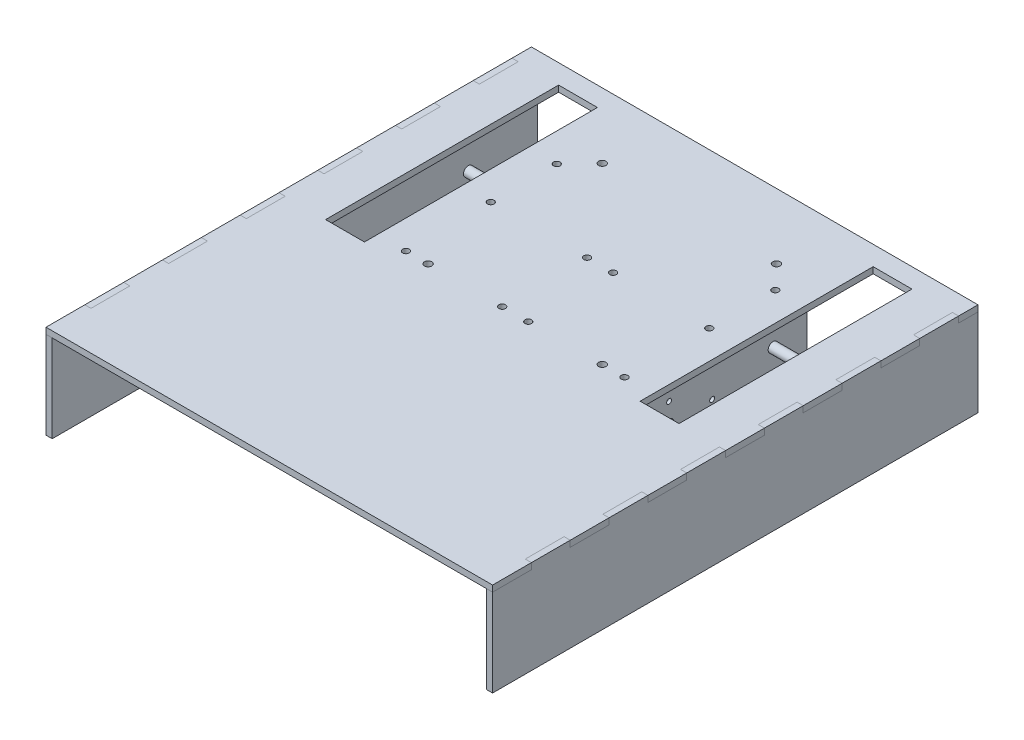
SolidWorks part; units mm, degrees
ref_plane "Front Plane" through (0, 0, 0) normal (0, 0, 1) x (1, 0, 0)
ref_plane "Top Plane" through (0, 0, 0) normal (0, 1, 0) x (1, 0, 0)
ref_plane "Right Plane" through (0, 0, 0) normal (1, 0, 0) x (0, 0, -1)
sketch "Sketch2" plane through (0, 0, 0) normal (0, 1, 0) x (1, 0, 0)
  line L7 (-172.2662, -88.2141) -> (57.7338, -88.2141)
  line L8 (13.7338, 151.7859) -> (33.7338, 151.7859)
  line L9 (57.7338, -88.2141) -> (57.7338, -68.2141)
  line L10 (57.7338, -68.2141) -> (54.5588, -68.2141)
  line L11 (54.5588, -68.2141) -> (54.5588, -48.2141)
  line L12 (54.5588, -48.2141) -> (57.7338, -48.2141)
  line L13 (-172.2662, -88.2141) -> (-172.2662, -68.2141)
  line L14 (-172.2662, -68.2141) -> (-169.0912, -68.2141)
  line L15 (-169.0912, -68.2141) -> (-169.0912, -48.2141)
  line L16 (-169.0912, -48.2141) -> (-172.2662, -48.2141)
  line L17 (-172.2662, -48.2141) -> (-172.2662, -28.2141)
  line L18 (-172.2662, -28.2141) -> (-169.0912, -28.2141)
  line L19 (-169.0912, -28.2141) -> (-169.0912, -8.2141)
  line L20 (-169.0912, -8.2141) -> (-172.2662, -8.2141)
  line L21 (57.7338, -28.2141) -> (54.5588, -28.2141)
  line L22 (54.5588, -28.2141) -> (54.5588, -8.2141)
  line L23 (54.5588, -8.2141) -> (57.7338, -8.2141)
  line L24 (57.7338, -48.2141) -> (57.7338, -28.2141)
  line L25 (-172.2662, -8.2141) -> (-172.2662, 11.7859)
  line L26 (-172.2662, 11.7859) -> (-169.0912, 11.7859)
  line L27 (-169.0912, 11.7859) -> (-169.0912, 31.7859)
  line L28 (-169.0912, 31.7859) -> (-172.2662, 31.7859)
  line L29 (57.7338, 11.7859) -> (54.5588, 11.7859)
  line L30 (54.5588, 11.7859) -> (54.5588, 31.7859)
  line L31 (54.5588, 31.7859) -> (57.7338, 31.7859)
  line L32 (57.7338, -8.2141) -> (57.7338, 11.7859)
  line L33 (-172.2662, 31.7859) -> (-172.2662, 51.7859)
  line L34 (-172.2662, 51.7859) -> (-169.0912, 51.7859)
  line L35 (-169.0912, 51.7859) -> (-169.0912, 71.7859)
  line L36 (-169.0912, 71.7859) -> (-172.2662, 71.7859)
  line L37 (57.7338, 51.7859) -> (54.5588, 51.7859)
  line L38 (54.5588, 51.7859) -> (54.5588, 71.7859)
  line L39 (54.5588, 71.7859) -> (57.7338, 71.7859)
  line L40 (57.7338, 31.7859) -> (57.7338, 51.7859)
  line L45 (13.7338, 151.7859) -> (13.7338, 31.7859)
  line L46 (13.7338, 31.7859) -> (33.7338, 31.7859)
  line L47 (33.7338, 151.7859) -> (33.7338, 31.7859)
  line L48 (-148.2662, 151.7859) -> (-128.2662, 151.7859)
  line L49 (-148.2662, 151.7859) -> (-148.2662, 31.7859)
  line L50 (-148.2662, 31.7859) -> (-128.2662, 31.7859)
  line L51 (-128.2662, 151.7859) -> (-128.2662, 31.7859)
  line L52 (-172.2662, 71.7859) -> (-172.2662, 91.7859)
  line L53 (-172.2662, 91.7859) -> (-169.0912, 91.7859)
  line L54 (-169.0912, 91.7859) -> (-169.0912, 111.7859)
  line L55 (-169.0912, 111.7859) -> (-172.2662, 111.7859)
  line L56 (57.7338, 91.7859) -> (54.5588, 91.7859)
  line L57 (54.5588, 91.7859) -> (54.5588, 111.7859)
  line L58 (54.5588, 111.7859) -> (57.7338, 111.7859)
  line L59 (57.7338, 71.7859) -> (57.7338, 91.7859)
  line L63 (-172.2662, 111.7859) -> (-172.2662, 131.7859)
  line L64 (-172.2662, 131.7859) -> (-169.0912, 131.7859)
  line L65 (-169.0912, 131.7859) -> (-169.0912, 151.7859)
  line L66 (-169.0912, 151.7859) -> (-172.2662, 151.7859)
  line L67 (57.7338, 131.7859) -> (54.5588, 131.7859)
  line L68 (54.5588, 131.7859) -> (54.5588, 151.7859)
  line L69 (54.5588, 151.7859) -> (57.7338, 151.7859)
  line L70 (57.7338, 111.7859) -> (57.7338, 131.7859)
  line L71 (57.7338, 151.7859) -> (57.7338, 161.7859)
  line L72 (57.7338, 161.7859) -> (-172.2662, 161.7859)
  line L73 (-172.2662, 161.7859) -> (-172.2662, 151.7859)
  dimension "D1" = 3.175
  dimension "D2" = 20
  dimension "D3" = 20
  dimension "D4" = 3.175
  dimension "D6" = 230
  dimension "D8" = 20
  dimension "D9" = 20
  dimension "D10" = 24
  dimension "D11" = 24
  dimension "D13" = 120
  dimension "D7" = 10
  dimension "D12" = 10
  dimension "D5" = 6
extrude "Boss-Extrude1" add sketch "Sketch2" along normal blind 3.175
ref_plane "Plane3" through (-57.2662, 0, 0) normal (-1, 0, 0) x (0, 0, 1)
sketch "Sketch3" plane through (-169.0912, 0, 0) normal (-1, 0, 0) x (0, 0, 1)
  line L0 (68.2141, 3.175) -> (68.2141, 0)
  line L1 (68.2141, 0) -> (88.2141, 0)
  line L2 (88.2141, 0) -> (88.2141, -45)
  line L3 (68.2141, 3.175) -> (48.2141, 3.175)
  line L4 (48.2141, 3.175) -> (48.2141, 0)
  line L5 (48.2141, 0) -> (28.2141, 0)
  line L6 (28.2141, 0) -> (28.2141, 3.175)
  line L7 (28.2141, 3.175) -> (8.2141, 3.175)
  line L8 (8.2141, 3.175) -> (8.2141, 0)
  line L9 (8.2141, 0) -> (-11.7859, 0)
  line L10 (-11.7859, 0) -> (-11.7859, 3.175)
  line L11 (-91.7859, 0) -> (-91.7859, 3.175)
  line L12 (-11.7859, 3.175) -> (-31.7859, 3.175)
  line L13 (-31.7859, 3.175) -> (-31.7859, 0)
  line L14 (-31.7859, 0) -> (-51.7859, 0)
  line L15 (-51.7859, 0) -> (-51.7859, 3.175)
  line L16 (-51.7859, 3.175) -> (-71.7859, 3.175)
  line L17 (-71.7859, 3.175) -> (-71.7859, 0)
  line L18 (-71.7859, 0) -> (-91.7859, 0)
  line L21 (-91.7859, 3.175) -> (-111.7859, 3.175)
  line L22 (-111.7859, 3.175) -> (-111.7859, 0)
  line L25 (-111.7859, 0) -> (-131.7859, 0)
  line L26 (-151.7859, 0) -> (-131.7859, 0) construction
  line L27 (-131.7859, 3.175) -> (-131.7859, 0) construction
  line L28 (-131.7859, 0) -> (-131.7859, 3.175)
  line L29 (-131.7859, 3.175) -> (-151.7859, 3.175)
  line L30 (-151.7859, 3.175) -> (-151.7859, 0)
  line L31 (-151.7859, 3.175) -> (-151.7859, 0) construction
  line L32 (-151.7859, 0) -> (-161.732, 0)
  line L33 (-161.732, 0) -> (-161.732, -45)
  line L34 (-161.732, -45) -> (88.2141, -45)
extrude "Boss-Extrude2" add sketch "Sketch3" along normal blind 3.175 separate body
sketch "Sketch4" plane through (0, 0, 0) normal (0, -1, 0) x (1, 0, 0)
  line L0 (-123.2662, -122.8126) -> (-123.2662, -33.6081)
  line L1 (-123.2662, -122.8126) -> (-105.4256, -122.8126)
  line L2 (-123.2662, -33.6081) -> (-108.8507, -33.6081)
  line L5 (-59.765, -32.9867) -> (-59.765, -87.1773)
  line L6 (-59.765, -32.9867) -> (-68.1795, -32.9867)
  line L7 (-59.765, -87.1773) -> (-68.1795, -87.1773)
  line L9 (-108.8507, -33.6081) -> (-105.4287, -55.4044)
  line L10 (-105.4287, -55.4044) -> (-68.1795, -55.4044)
  line L11 (-68.1795, -55.4044) -> (-68.1795, -32.9867)
  line L12 (-68.1795, -87.1773) -> (-68.1795, -65.4044)
  line L13 (-68.1795, -65.4044) -> (-105.4256, -65.4044)
  line L14 (-105.4256, -65.4044) -> (-105.4256, -122.8126)
  point P0 (-108.8507, -33.6081)
extrude "Boss-Extrude3" add sketch "Sketch4" along normal blind 1.6129 separate body
sketch "Sketch6" plane through (-123.2662, 113.8349, 0) normal (1, 0, 0) x (0, -1, 0)
  line L0 (115.4478, 33.6081) -> (113.8349, 33.6081)
  line L1 (113.8349, 33.6081) -> (113.8349, 122.8126)
  line L4 (133.4041, 33.6081) -> (115.4478, 33.6081)
  line L7 (135.7395, 122.8126) -> (113.8349, 122.8126)
  line L8 (113.8349, 31.7859) -> (113.8349, 151.7859) construction
  line L10 (115.4478, 122.8126) -> (113.8349, 122.8126) construction
  line L11 (135.7395, 122.8126) -> (135.7395, 87.0987)
  circle A2 centre (133.4041, 73.86) radius 1.27
  arc A3 (133.4041, 33.6081) -> (135.7395, 87.0987) centre (133.4041, 60.4044) ccw
  circle A4 centre (133.4041, 51.6858) radius 2.3749
  circle A5 centre (125.8349, 105.2548) radius 2.55
  circle A6 centre (123.1933, 51.6858) radius 1.27
  circle A8 centre (143.6149, 51.6858) radius 1.27
  circle A11 centre (133.4041, 60.4044) radius 17.5692
  line M25 (113.8349, 33.6081) -> (113.8349, 122.8126)
  line M26 (113.8349, 122.8126) -> (115.4478, 122.8126)
  line M27 (115.4478, 122.8126) -> (115.4478, 33.6081)
  line M28 (115.4478, 33.6081) -> (113.8349, 33.6081)
  dimension "D1" = 5.1
  dimension "D2" = 12
extrude "Boss-Extrude4" add sketch "Sketch6" along normal blind 1.6129 contours M28 M25 M26 M27 | L4 A11 M27 | A11 A6 A2 A4 A8 region at (-123.2662, -2.6109, -78.2104) region at (-123.2662, -0.8064, -78.2104) region at (-123.2662, -19.5692, -60.5908)
sketch "Sketch7" plane through (0, -1.6129, 0) normal (0, -1, 0) x (1, 0, 0)
  circle A0 centre (-113.5394, -82.125) radius 1.7
  circle A1 centre (-113.5394, -38.4299) radius 1.7
  circle A2 centre (-63.9723, -38.4299) radius 1.7
  circle A3 centre (-63.9723, -82.125) radius 1.7
  circle A4 centre (-113.5394, -116.1203) radius 1.7
  circle A5 centre (-102.1184, -38.4299) radius 1.9
  circle A6 centre (-102.1184, -128.1299) radius 1.9
  point P10 (0, 0)
  point P13 (0, 0)
  point P14 (0, 0)
  point P17 (0, 0)
  dimension "D3" = 3.4
  dimension "D4" = 3.4
  dimension "D5" = 3.4
  dimension "D6" = 3.4
  dimension "D1" = 3.4
  dimension "D2" = 3.8
  dimension "D8" = 3.8
  dimension "D7" = 89.7
extrude "Cut-Extrude1" cut sketch "Sketch7" against normal blind 10
mirror "Mirror1" about plane through (-57.2662, 0, 0) normal (-1, 0, 0) of bodies 157 103 158
mirror "Mirror2" about plane through (-57.2662, 0, 0) normal (-1, 0, 0) of "Cut-Extrude1"
sketch "Sketch9" plane through (-148.2662, 0, 0) normal (1, 0, 0) x (0, 0, -1)
  circle A0 centre (105.2548, -12) radius 2.5
extrude "Boss-Extrude6" add sketch "Sketch9" along normal blind 189 separate body
equation "\"hardboard_width\"= 3.175"
equation "\"D1@Boss-Extrude1\"=\"hardboard_width\""
equation "\"D1@Sketch2\"=\"hardboard_width\""
equation "\"D4@Sketch2\"=\"hardboard_width\""
equation "\"D1@Boss-Extrude2\"=\"hardboard_width\""
equation "\"steel_24g_thickness\"= 0.5"
equation "\"m3_clearance_hole\"= 3.4"
equation "\"D3@Sketch7\"=\"m3_clearance_hole\""
equation "\"D4@Sketch7\"=\"m3_clearance_hole\""
equation "\"D5@Sketch7\"=\"m3_clearance_hole\""
equation "\"D6@Sketch7\"=\"m3_clearance_hole\""
equation "\"steel_16g_thickness\"=1.6129"
equation "\"D1@Boss-Extrude3\"=\"steel_16g_thickness\""
equation "\"D1@Boss-Extrude4\"=\"steel_16g_thickness\""
equation "\"D1@Sketch7\"=\"m3_clearance_hole\""
